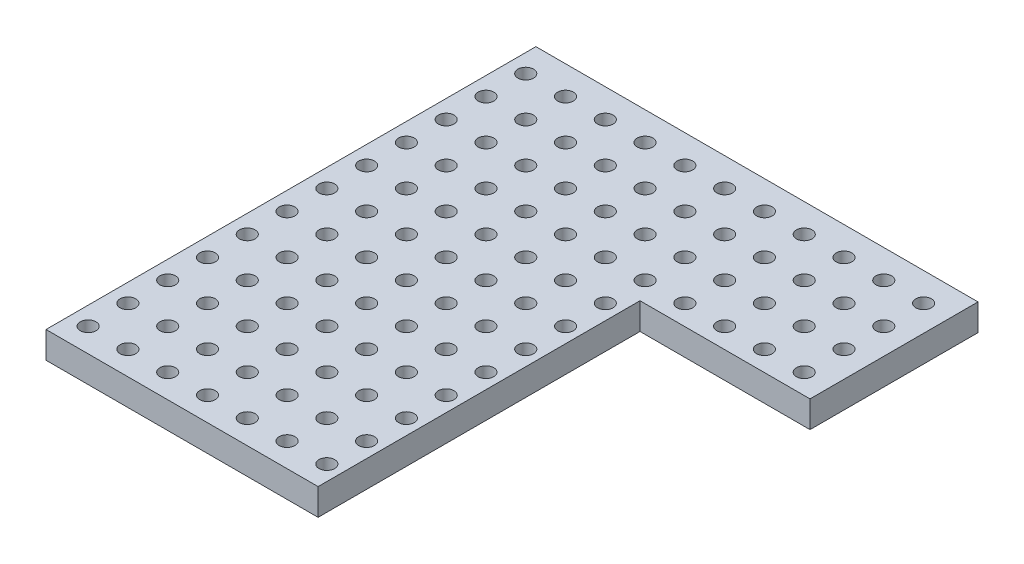
SolidWorks part; units mm, degrees
material "Copper"
ref_plane "Front Plane" through (0, 0, 0) normal (0, 0, 1) x (1, 0, 0)
ref_plane "Top Plane" through (0, 0, 0) normal (0, 1, 0) x (1, 0, 0)
ref_plane "Right Plane" through (0, 0, 0) normal (1, 0, 0) x (0, 0, -1)
sketch "Sketch1" plane through (0, 0, 0) normal (0, 1, 0) x (1, 0, 0)
  line L1 (30, -20) -> (-30, -20)
  line L2 (30, -20) -> (30, 20)
  line L3 (30, 20) -> (-30, 20)
  line L4 (-30, -20) -> (-30, 20)
  circle A0 centre (24.158, 16.571) radius 0.5
  circle A1 centre (21.618, 16.571) radius 0.5
  circle A2 centre (19.078, 16.571) radius 0.5
  circle A3 centre (16.538, 16.571) radius 0.5
  circle A4 centre (13.998, 16.571) radius 0.5
  circle A5 centre (11.458, 16.571) radius 0.5
  circle A6 centre (8.918, 16.571) radius 0.5
  circle A7 centre (6.378, 16.571) radius 0.5
  circle A8 centre (3.838, 16.571) radius 0.5
  circle A9 centre (1.298, 16.571) radius 0.5
  circle A10 centre (-1.242, 16.571) radius 0.5
  circle A11 centre (-3.782, 16.571) radius 0.5
  circle A12 centre (-6.322, 16.571) radius 0.5
  circle A13 centre (-8.862, 16.571) radius 0.5
  circle A14 centre (-11.402, 16.571) radius 0.5
  circle A15 centre (-13.942, 16.571) radius 0.5
  circle A16 centre (-16.482, 16.571) radius 0.5
  circle A17 centre (-19.022, 16.571) radius 0.5
  circle A18 centre (-21.562, 16.571) radius 0.5
  circle A19 centre (-24.102, 16.571) radius 0.5
  circle A20 centre (21.618, 14.031) radius 0.5
  circle A21 centre (19.078, 14.031) radius 0.5
  circle A22 centre (16.538, 14.031) radius 0.5
  circle A23 centre (13.998, 14.031) radius 0.5
  circle A24 centre (11.458, 14.031) radius 0.5
  circle A25 centre (8.918, 14.031) radius 0.5
  circle A26 centre (6.378, 14.031) radius 0.5
  circle A27 centre (3.838, 14.031) radius 0.5
  circle A28 centre (1.298, 14.031) radius 0.5
  circle A29 centre (-1.242, 14.031) radius 0.5
  circle A30 centre (-3.782, 14.031) radius 0.5
  circle A31 centre (-6.322, 14.031) radius 0.5
  circle A32 centre (-8.862, 14.031) radius 0.5
  circle A33 centre (-11.402, 14.031) radius 0.5
  circle A34 centre (-13.942, 14.031) radius 0.5
  circle A35 centre (-16.482, 14.031) radius 0.5
  circle A36 centre (-19.022, 14.031) radius 0.5
  circle A37 centre (-21.562, 14.031) radius 0.5
  circle A38 centre (-24.102, 14.031) radius 0.5
  circle A39 centre (21.618, 11.491) radius 0.5
  circle A40 centre (19.078, 11.491) radius 0.5
  circle A41 centre (16.538, 11.491) radius 0.5
  circle A42 centre (13.998, 11.491) radius 0.5
  circle A43 centre (11.458, 11.491) radius 0.5
  circle A44 centre (8.918, 11.491) radius 0.5
  circle A45 centre (6.378, 11.491) radius 0.5
  circle A46 centre (3.838, 11.491) radius 0.5
  circle A47 centre (1.298, 11.491) radius 0.5
  circle A48 centre (-1.242, 11.491) radius 0.5
  circle A49 centre (-3.782, 11.491) radius 0.5
  circle A50 centre (-6.322, 11.491) radius 0.5
  circle A51 centre (-8.862, 11.491) radius 0.5
  circle A52 centre (-11.402, 11.491) radius 0.5
  circle A53 centre (-13.942, 11.491) radius 0.5
  circle A54 centre (-16.482, 11.491) radius 0.5
  circle A55 centre (-19.022, 11.491) radius 0.5
  circle A56 centre (-21.562, 11.491) radius 0.5
  circle A57 centre (-24.102, 11.491) radius 0.5
  circle A58 centre (21.618, 8.951) radius 0.5
  circle A59 centre (19.078, 8.951) radius 0.5
  circle A60 centre (16.538, 8.951) radius 0.5
  circle A61 centre (13.998, 8.951) radius 0.5
  circle A62 centre (11.458, 8.951) radius 0.5
  circle A63 centre (8.918, 8.951) radius 0.5
  circle A64 centre (6.378, 8.951) radius 0.5
  circle A65 centre (3.838, 8.951) radius 0.5
  circle A66 centre (1.298, 8.951) radius 0.5
  circle A67 centre (-1.242, 8.951) radius 0.5
  circle A68 centre (-3.782, 8.951) radius 0.5
  circle A69 centre (-6.322, 8.951) radius 0.5
  circle A70 centre (-8.862, 8.951) radius 0.5
  circle A71 centre (-11.402, 8.951) radius 0.5
  circle A72 centre (-13.942, 8.951) radius 0.5
  circle A73 centre (-16.482, 8.951) radius 0.5
  circle A74 centre (-19.022, 8.951) radius 0.5
  circle A75 centre (-21.562, 8.951) radius 0.5
  circle A76 centre (-24.102, 8.951) radius 0.5
  circle A77 centre (21.618, 6.411) radius 0.5
  circle A78 centre (19.078, 6.411) radius 0.5
  circle A79 centre (16.538, 6.411) radius 0.5
  circle A80 centre (13.998, 6.411) radius 0.5
  circle A81 centre (11.458, 6.411) radius 0.5
  circle A82 centre (8.918, 6.411) radius 0.5
  circle A83 centre (6.378, 6.411) radius 0.5
  circle A84 centre (3.838, 6.411) radius 0.5
  circle A85 centre (1.298, 6.411) radius 0.5
  circle A86 centre (-1.242, 6.411) radius 0.5
  circle A87 centre (-3.782, 6.411) radius 0.5
  circle A88 centre (-6.322, 6.411) radius 0.5
  circle A89 centre (-8.862, 6.411) radius 0.5
  circle A90 centre (-11.402, 6.411) radius 0.5
  circle A91 centre (-13.942, 6.411) radius 0.5
  circle A92 centre (-16.482, 6.411) radius 0.5
  circle A93 centre (-19.022, 6.411) radius 0.5
  circle A94 centre (-21.562, 6.411) radius 0.5
  circle A95 centre (-24.102, 6.411) radius 0.5
  circle A96 centre (21.618, 3.871) radius 0.5
  circle A97 centre (19.078, 3.871) radius 0.5
  circle A98 centre (16.538, 3.871) radius 0.5
  circle A99 centre (13.998, 3.871) radius 0.5
  circle A100 centre (11.458, 3.871) radius 0.5
  circle A101 centre (8.918, 3.871) radius 0.5
  circle A102 centre (6.378, 3.871) radius 0.5
  circle A103 centre (3.838, 3.871) radius 0.5
  circle A104 centre (1.298, 3.871) radius 0.5
  circle A105 centre (-1.242, 3.871) radius 0.5
  circle A106 centre (-3.782, 3.871) radius 0.5
  circle A107 centre (-6.322, 3.871) radius 0.5
  circle A108 centre (-8.862, 3.871) radius 0.5
  circle A109 centre (-11.402, 3.871) radius 0.5
  circle A110 centre (-13.942, 3.871) radius 0.5
  circle A111 centre (-16.482, 3.871) radius 0.5
  circle A112 centre (-19.022, 3.871) radius 0.5
  circle A113 centre (-21.562, 3.871) radius 0.5
  circle A114 centre (-24.102, 3.871) radius 0.5
  circle A115 centre (21.618, 1.331) radius 0.5
  circle A116 centre (19.078, 1.331) radius 0.5
  circle A117 centre (16.538, 1.331) radius 0.5
  circle A118 centre (13.998, 1.331) radius 0.5
  circle A119 centre (11.458, 1.331) radius 0.5
  circle A120 centre (8.918, 1.331) radius 0.5
  circle A121 centre (6.378, 1.331) radius 0.5
  circle A122 centre (3.838, 1.331) radius 0.5
  circle A123 centre (1.298, 1.331) radius 0.5
  circle A124 centre (-1.242, 1.331) radius 0.5
  circle A125 centre (-3.782, 1.331) radius 0.5
  circle A126 centre (-6.322, 1.331) radius 0.5
  circle A127 centre (-8.862, 1.331) radius 0.5
  circle A128 centre (-11.402, 1.331) radius 0.5
  circle A129 centre (-13.942, 1.331) radius 0.5
  circle A130 centre (-16.482, 1.331) radius 0.5
  circle A131 centre (-19.022, 1.331) radius 0.5
  circle A132 centre (-21.562, 1.331) radius 0.5
  circle A133 centre (-24.102, 1.331) radius 0.5
  circle A134 centre (21.618, -1.209) radius 0.5
  circle A135 centre (19.078, -1.209) radius 0.5
  circle A136 centre (16.538, -1.209) radius 0.5
  circle A137 centre (13.998, -1.209) radius 0.5
  circle A138 centre (11.458, -1.209) radius 0.5
  circle A139 centre (8.918, -1.209) radius 0.5
  circle A140 centre (6.378, -1.209) radius 0.5
  circle A141 centre (3.838, -1.209) radius 0.5
  circle A142 centre (1.298, -1.209) radius 0.5
  circle A143 centre (-1.242, -1.209) radius 0.5
  circle A144 centre (-3.782, -1.209) radius 0.5
  circle A145 centre (-6.322, -1.209) radius 0.5
  circle A146 centre (-8.862, -1.209) radius 0.5
  circle A147 centre (-11.402, -1.209) radius 0.5
  circle A148 centre (-13.942, -1.209) radius 0.5
  circle A149 centre (-16.482, -1.209) radius 0.5
  circle A150 centre (-19.022, -1.209) radius 0.5
  circle A151 centre (-21.562, -1.209) radius 0.5
  circle A152 centre (-24.102, -1.209) radius 0.5
  circle A153 centre (21.618, -3.749) radius 0.5
  circle A154 centre (19.078, -3.749) radius 0.5
  circle A155 centre (16.538, -3.749) radius 0.5
  circle A156 centre (13.998, -3.749) radius 0.5
  circle A157 centre (11.458, -3.749) radius 0.5
  circle A158 centre (8.918, -3.749) radius 0.5
  circle A159 centre (6.378, -3.749) radius 0.5
  circle A160 centre (3.838, -3.749) radius 0.5
  circle A161 centre (1.298, -3.749) radius 0.5
  circle A162 centre (-1.242, -3.749) radius 0.5
  circle A163 centre (-3.782, -3.749) radius 0.5
  circle A164 centre (-6.322, -3.749) radius 0.5
  circle A165 centre (-8.862, -3.749) radius 0.5
  circle A166 centre (-11.402, -3.749) radius 0.5
  circle A167 centre (-13.942, -3.749) radius 0.5
  circle A168 centre (-16.482, -3.749) radius 0.5
  circle A169 centre (-19.022, -3.749) radius 0.5
  circle A170 centre (-21.562, -3.749) radius 0.5
  circle A171 centre (-24.102, -3.749) radius 0.5
  circle A172 centre (21.618, -6.289) radius 0.5
  circle A173 centre (19.078, -6.289) radius 0.5
  circle A174 centre (16.538, -6.289) radius 0.5
  circle A175 centre (13.998, -6.289) radius 0.5
  circle A176 centre (11.458, -6.289) radius 0.5
  circle A177 centre (8.918, -6.289) radius 0.5
  circle A178 centre (6.378, -6.289) radius 0.5
  circle A179 centre (3.838, -6.289) radius 0.5
  circle A180 centre (1.298, -6.289) radius 0.5
  circle A181 centre (-1.242, -6.289) radius 0.5
  circle A182 centre (-3.782, -6.289) radius 0.5
  circle A183 centre (-6.322, -6.289) radius 0.5
  circle A184 centre (-8.862, -6.289) radius 0.5
  circle A185 centre (-11.402, -6.289) radius 0.5
  circle A186 centre (-13.942, -6.289) radius 0.5
  circle A187 centre (-16.482, -6.289) radius 0.5
  circle A188 centre (-19.022, -6.289) radius 0.5
  circle A189 centre (-21.562, -6.289) radius 0.5
  circle A190 centre (-24.102, -6.289) radius 0.5
  circle A191 centre (21.618, -8.829) radius 0.5
  circle A192 centre (19.078, -8.829) radius 0.5
  circle A193 centre (16.538, -8.829) radius 0.5
  circle A194 centre (13.998, -8.829) radius 0.5
  circle A195 centre (11.458, -8.829) radius 0.5
  circle A196 centre (8.918, -8.829) radius 0.5
  circle A197 centre (6.378, -8.829) radius 0.5
  circle A198 centre (3.838, -8.829) radius 0.5
  circle A199 centre (1.298, -8.829) radius 0.5
  circle A200 centre (-1.242, -8.829) radius 0.5
  circle A201 centre (-3.782, -8.829) radius 0.5
  circle A202 centre (-6.322, -8.829) radius 0.5
  circle A203 centre (-8.862, -8.829) radius 0.5
  circle A204 centre (-11.402, -8.829) radius 0.5
  circle A205 centre (-13.942, -8.829) radius 0.5
  circle A206 centre (-16.482, -8.829) radius 0.5
  circle A207 centre (-19.022, -8.829) radius 0.5
  circle A208 centre (-21.562, -8.829) radius 0.5
  circle A209 centre (-24.102, -8.829) radius 0.5
  circle A210 centre (21.618, -11.369) radius 0.5
  circle A211 centre (19.078, -11.369) radius 0.5
  circle A212 centre (16.538, -11.369) radius 0.5
  circle A213 centre (13.998, -11.369) radius 0.5
  circle A214 centre (11.458, -11.369) radius 0.5
  circle A215 centre (8.918, -11.369) radius 0.5
  circle A216 centre (6.378, -11.369) radius 0.5
  circle A217 centre (3.838, -11.369) radius 0.5
  circle A218 centre (1.298, -11.369) radius 0.5
  circle A219 centre (-1.242, -11.369) radius 0.5
  circle A220 centre (-3.782, -11.369) radius 0.5
  circle A221 centre (-6.322, -11.369) radius 0.5
  circle A222 centre (-8.862, -11.369) radius 0.5
  circle A223 centre (-11.402, -11.369) radius 0.5
  circle A224 centre (-13.942, -11.369) radius 0.5
  circle A225 centre (-16.482, -11.369) radius 0.5
  circle A226 centre (-19.022, -11.369) radius 0.5
  circle A227 centre (-21.562, -11.369) radius 0.5
  circle A228 centre (-24.102, -11.369) radius 0.5
  circle A229 centre (21.618, -13.909) radius 0.5
  circle A230 centre (19.078, -13.909) radius 0.5
  circle A231 centre (16.538, -13.909) radius 0.5
  circle A232 centre (13.998, -13.909) radius 0.5
  circle A233 centre (11.458, -13.909) radius 0.5
  circle A234 centre (8.918, -13.909) radius 0.5
  circle A235 centre (6.378, -13.909) radius 0.5
  circle A236 centre (3.838, -13.909) radius 0.5
  circle A237 centre (1.298, -13.909) radius 0.5
  circle A238 centre (-1.242, -13.909) radius 0.5
  circle A239 centre (-3.782, -13.909) radius 0.5
  circle A240 centre (-6.322, -13.909) radius 0.5
  circle A241 centre (-8.862, -13.909) radius 0.5
  circle A242 centre (-11.402, -13.909) radius 0.5
  circle A243 centre (-13.942, -13.909) radius 0.5
  circle A244 centre (-16.482, -13.909) radius 0.5
  circle A245 centre (-19.022, -13.909) radius 0.5
  circle A246 centre (-21.562, -13.909) radius 0.5
  circle A247 centre (-24.102, -13.909) radius 0.5
  circle A248 centre (21.618, -16.449) radius 0.5
  circle A249 centre (19.078, -16.449) radius 0.5
  circle A250 centre (16.538, -16.449) radius 0.5
  circle A251 centre (13.998, -16.449) radius 0.5
  circle A252 centre (11.458, -16.449) radius 0.5
  circle A253 centre (8.918, -16.449) radius 0.5
  circle A254 centre (6.378, -16.449) radius 0.5
  circle A255 centre (3.838, -16.449) radius 0.5
  circle A256 centre (1.298, -16.449) radius 0.5
  circle A257 centre (-1.242, -16.449) radius 0.5
  circle A258 centre (-3.782, -16.449) radius 0.5
  circle A259 centre (-6.322, -16.449) radius 0.5
  circle A260 centre (-8.862, -16.449) radius 0.5
  circle A261 centre (-11.402, -16.449) radius 0.5
  circle A262 centre (-13.942, -16.449) radius 0.5
  circle A263 centre (-16.482, -16.449) radius 0.5
  circle A264 centre (-19.022, -16.449) radius 0.5
  circle A265 centre (-21.562, -16.449) radius 0.5
  circle A266 centre (-24.102, -16.449) radius 0.5
  circle A267 centre (24.158, 14.031) radius 0.5
  circle A268 centre (24.158, 11.491) radius 0.5
  circle A269 centre (24.158, 8.951) radius 0.5
  circle A270 centre (24.158, 6.411) radius 0.5
  circle A271 centre (24.158, 3.871) radius 0.5
  circle A272 centre (24.158, 1.331) radius 0.5
  circle A273 centre (24.158, -1.209) radius 0.5
  circle A274 centre (24.158, -3.749) radius 0.5
  circle A275 centre (24.158, -6.289) radius 0.5
  circle A276 centre (24.158, -8.829) radius 0.5
  circle A277 centre (24.158, -11.369) radius 0.5
  circle A278 centre (24.158, -13.909) radius 0.5
  circle A279 centre (24.158, -16.449) radius 0.5
  point P0 (0, 0)
  dimension "D3" = 1
  dimension "D1" = 40
  dimension "D2" = 60
  dimension "D6" = 3.429
  dimension "D7" = 5.842
  dimension "D4" = 20
  dimension "D5" = 14
extrude "Boss-Extrude1" add sketch "Sketch1" along normal blind 1.7018
sketch "Sketch2" plane through (0, 1.7018, 0) normal (0, 1, 0) x (1, 0, 0)
  line L0 (-2.409, 18.3868) -> (25.8181, 18.3868)
  line L1 (25.8181, 18.3868) -> (25.8181, 7.6607)
  line L2 (25.8181, 7.6607) -> (14.964, 7.6607)
  line L3 (14.964, 7.6607) -> (14.964, -12.8927)
  line L4 (14.964, -12.8927) -> (-2.409, -12.8927)
  line L5 (-2.409, -12.8927) -> (-2.409, 18.3868)
  line L7 (-30, 20) -> (30, 20)
  line L8 (-30, 20) -> (-30, -20)
  line L9 (-30, -20) -> (30, -20)
  line L10 (30, 20) -> (30, -20)
extrude "Cut-Extrude2" cut sketch "Sketch2" against normal through all contours L10 L7 L8 L9 L4 L5 L0 L1 L2 L3 region at (-3.3246, 1.7018, 1.7292)
other "CPoint1" parameters "Diameter"=0.635, "StubLength"=1.27
ref_axis "Axis1" through (-1.242, 11.7018, -11.491) along (0, -1, 0)
other "CPoint2" parameters "Diameter"=0.635, "StubLength"=0.9525
ref_axis "Axis2" through (-1.242, 11.7018, -16.571) along (0, -1, 0)
other "CPoint3" parameters "Diameter"=0.635, "StubLength"=0.9525
ref_axis "Axis3" through (-1.242, 11.7018, 11.369) along (0, -1, 0)
other "CPoint4" parameters "Diameter"=0.635, "StubLength"=0.9525
ref_axis "Axis4" through (-1.242, 11.7018, 6.289) along (0, -1, 0)
